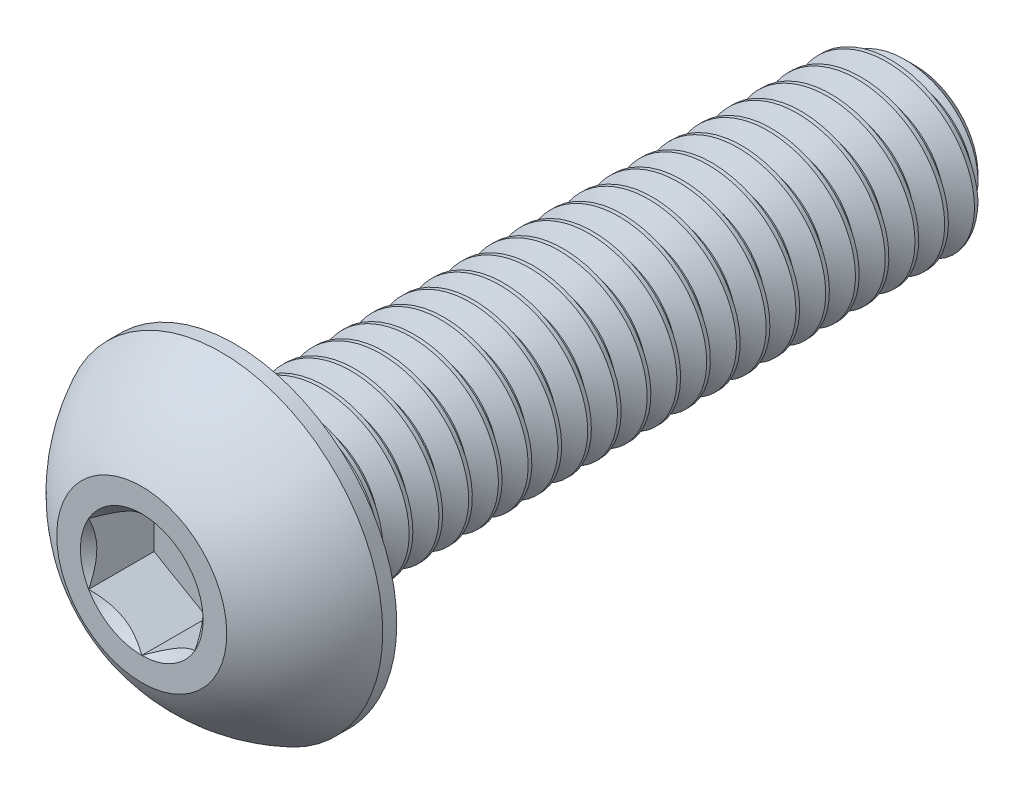
SolidWorks part; units mm, degrees
ref_plane "Front" through (0, 0, 0) normal (0, 0, 1) x (1, 0, 0)
ref_plane "Top" through (0, 0, 0) normal (0, 1, 0) x (1, 0, 0)
ref_plane "Right" through (0, 0, 0) normal (1, 0, 0) x (0, 0, -1)
sketch "Sketch1" plane through (0, 0, 0) normal (1, 0, 0) x (0, 0, -1)
  line L2 (2.2, 2) -> (18.2, 2)
  line L3 (18.2, 2) -> (18.2, 0)
  line L4 (18.2, 0) -> (2.2, 0)
  line L6 (1.87, 3.8) -> (2.2, 3.8) construction
  line L7 (18.2, 2) -> (18.2, -2) construction
  line L8 (0, 0) -> (2.2, 0) construction
  line L9 (2.2, 3.8) -> (2.2, -3.8) construction
  line L11 (2.2, 2) -> (2.2, 0)
  line L13 (0, 1.25) -> (0, -1.25) construction
  line L14 (0, 1.25) -> (0, 2) construction
  arc A3 (0, 2) -> (1.87, 3.8) centre (3.7264, 0) cw construction
  dimension "D1" = 0.33
  dimension "Head Ht" = 2.2
  dimension "Head Dia" = 7.6
  dimension "Dia" = 4
  dimension "Lg" = 16
  dimension "Hex" = 2.5
revolve "Revolve1" add sketch "Sketch1" angle 360 about L4
sketch "Sketch3" plane through (0, 0, -18.2) normal (0, 0, -1) x (-1, 0, 0)
  circle A0 centre (0, 0) radius 2
curve "Helix/Spiral1" pitch 0.7 height 18.2 radius 2 centre (0, 0, -18.2) axis (0, 0, 1) start towards (0, 1, 0)
sketch "Sketch2" plane through (0, 0, 0) normal (1, 0, 0) x (0, 0, -1)
  line L0 (18.2, 2) -> (18.8125, 2)
  line L1 (18.8125, 2) -> (18.55, 1.5453)
  line L2 (18.55, 1.5453) -> (18.4625, 1.5453)
  line L3 (18.4625, 1.5453) -> (18.2, 2)
  line L4 (18.3313, 1.7727) -> (18.6813, 1.7727) construction
  dimension "D1" = 60
  dimension "D2" = 0.0875
  dimension "D3" = 0.35
chamfer "Chamfer1" distance 0.525 angle 45 1 edges at (0, 2, -18.2)
sweep "Cut-Sweep1" cut profiles "Sketch2" path "Helix/Spiral1"
sketch "Sketch7" plane through (0, 0, 0) normal (1, 0, 0) x (0, 0, -1)
  line L6 (1.87, 3.8) -> (2.2, 3.8) construction
  line L8 (0, 0) -> (2.2, 0) construction
  line L11 (2.2, 3.8) -> (2.2, -3.8) construction
  line L12 (1.87, 3.8) -> (2.2, 3.8)
  line L13 (0, 0) -> (2.2, 0)
  line L14 (0, 1.25) -> (0, -1.25) construction
  line L15 (2.2, 3.8) -> (2.2, 0)
  line L16 (0, 2) -> (0, 0)
  arc A2 (1.87, 3.8) -> (0, 2) centre (3.7264, 0) ccw construction
  arc A3 (1.87, 3.8) -> (0, 2) centre (3.7264, 0) ccw
revolve "Revolve2" add sketch "Sketch7" angle 360 about L13
sketch "Sketch5" plane through (0, 0, 0) normal (0, 0, 1) x (1, 0, 0)
  line L1 (1.25, -0.7217) -> (1.25, 0.7217)
  line L2 (1.25, 0.7217) -> (0, 1.4434)
  line L3 (0, 1.4434) -> (-1.25, 0.7217)
  line L4 (-1.25, 0.7217) -> (-1.25, -0.7217)
  line L5 (-1.25, -0.7217) -> (0, -1.4434)
  line L6 (0, -1.4434) -> (1.25, -0.7217)
  circle A0 centre (0, 0) radius 1.25 construction
extrude "Cut-Extrude2" cut sketch "Sketch5" against normal blind 1.54
sketch "Sketch6" plane through (0, 0, 0) normal (0, 0, 1) x (1, 0, 0)
  circle A0 centre (0, 0) radius 1.4434
extrude "Cut-Extrude3" cut sketch "Sketch6" against normal blind 1.54 draft 45
sketch "Sketch9" [suppressed] plane through (0, 0, -2.2) normal (0, 0, 1) x (1, 0, 0)
  circle A2 centre (0, 0) radius 1.5
extrude "Boss-Extrude2" [suppressed] add sketch "Sketch9" against normal offset from surface (20 mm away) 32 up to face at (0, 1.475, -18.2)
sketch "Sketch10" plane through (0, 0, 0) normal (1, 0, 0) x (0, 0, -1)
  line L0 (18.2, 2) -> (18.2, -2) construction
  point P0 (17.15, -2)
  dimension "D1" = 1.05
equation "\"D3@Helix/Spiral1\" = \"Lg@Sketch1\" + \"Head Ht@Sketch1\""
equation "\"D2@Sketch2\" = \"D4@Helix/Spiral1\" * .125"
equation "\"D3@Sketch2\" = \"D4@Helix/Spiral1\" * .5"
equation "\"D1@Chamfer1\" = \"D4@Helix/Spiral1\" * .75"
equation "\"D1@Cut-Extrude2\" = \"Head Ht@Sketch1\" * .7"
equation "\"D1@Sketch1\" = \"Head Ht@Sketch1\" * .15"
equation "\"D1@Sketch10\" = \"D4@Helix/Spiral1\" * 1.5"
equation "\"D1@Cut-Extrude3\" = \"D1@Cut-Extrude2\""
